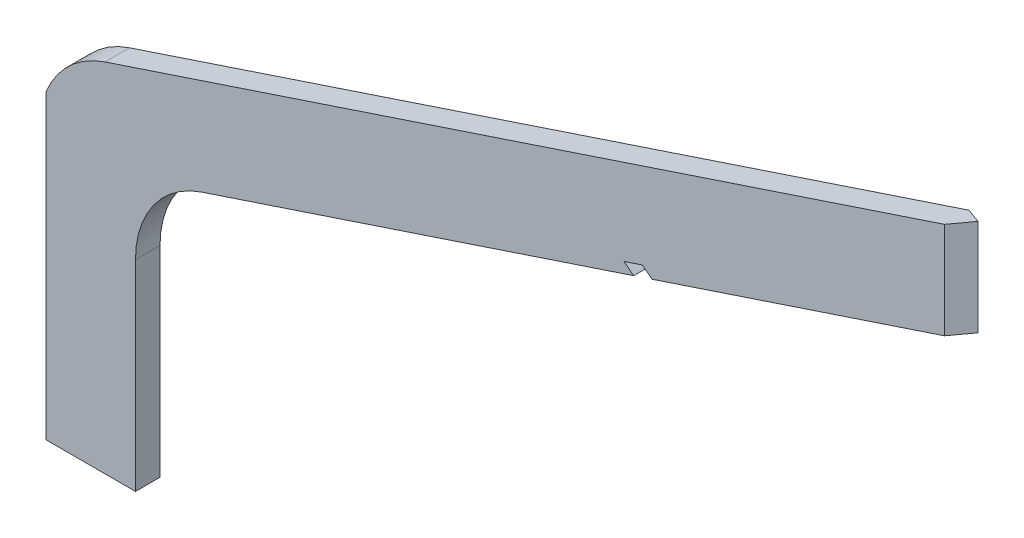
SolidWorks part; units mm, degrees
material "6061 Alloy"
ref_plane "Front Plane" through (0, 0, 0) normal (0, 0, 1) x (1, 0, 0)
ref_plane "Top Plane" through (0, 0, 0) normal (0, 1, 0) x (1, 0, 0)
ref_plane "Right Plane" through (0, 0, 0) normal (1, 0, 0) x (0, 0, -1)
sketch "Sketch1" plane through (0, 0, 0) normal (0, 0, 1) x (1, 0, 0)
  line L13 (-95.4803, -80.7064) -> (-95.4803, -131.0852)
  line L16 (-120.4803, -131.0852) -> (119.5197, -131.0852)
  line L17 (119.5197, 8.8096) -> (119.5197, 33.8096)
  line L18 (-78.3677, -56.9832) -> (119.5197, 8.8096)
  line L20 (119.5197, 8.8096) -> (119.5197, -131.0852)
  line L21 (119.5197, 33.8096) -> (-103.3677, -40.2951)
  line L22 (-120.4803, -64.0183) -> (-120.4803, -131.0852)
  line L23 (-120.4803, -131.0852) -> (-120.4803, -132.6727)
  line L24 (-120.4803, -132.6727) -> (-95.4803, -132.6727)
  line L25 (-95.4803, -132.6727) -> (-95.4803, -131.0852)
  arc A0 (-95.4803, -80.7064) -> (-78.3677, -56.9832) centre (-70.4803, -80.7064) cw
  arc A1 (-120.4803, -64.0183) -> (-103.3677, -40.2951) centre (-95.4803, -64.0183) cw
  dimension "D5" = 25
  dimension "D1" = 25
  dimension "D2" = 240
  dimension "D3" = 139.8948
  dimension "D4" = 25
extrude "Boss-Extrude1" add sketch "Sketch1" along normal blind 3.175 and the other way blind 3.175 contours L17 L21 A1 L22 L23 L24 L25 L13 A0 L18
sketch "Sketch2" plane through (0, -132.6727, 0) normal (0, -1, 0) x (1, 0, 0)
  line L10 (-120.4803, 0) -> (-120.4803, 3.175)
  line L12 (-120.4803, 3.175) -> (-118.6472, 3.175)
  line L14 (-120.4803, 0) -> (-118.6472, 3.175)
extrude "Cut-Extrude3" cut sketch "Sketch2" against normal through all
mirror "Mirror3" about plane through (0, 0, 0) normal (0, 0, 1) of "Cut-Extrude3"
sketch "Sketch3" plane through (0, -132.6727, 0) normal (0, -1, 0) x (1, 0, 0)
  line L1 (119.5197, 3.175) -> (114.0204, 3.175)
  line L5 (119.5197, 3.175) -> (119.5197, 0)
  line L6 (119.5197, -3.175) -> (119.5197, 3.175) construction
  line L7 (119.5197, 0) -> (114.0204, 3.175)
extrude "Cut-Extrude5" cut sketch "Sketch3" against normal through all
mirror "Mirror4" about plane through (0, 0, 0) normal (0, 0, 1) of "Cut-Extrude5"
sketch "Sketch6" plane through (0, 0, 3.175) normal (0, 0, 1) x (1, 0, 0)
  line L0 (33.5465, -19.7744) -> (38.2911, -18.197)
  line L8 (33.5465, -19.7744) -> (31.0251, -17.8449)
  line L9 (31.0251, -17.8449) -> (35.7697, -16.2674)
  line L11 (35.7697, -16.2674) -> (38.2911, -18.197)
extrude "Cut-Extrude6" cut sketch "Sketch6" against normal up to surface (6.35 mm away) contours L9 L11 L0 L8 up to face at (-48.4192, -56.8185, -3.175)
